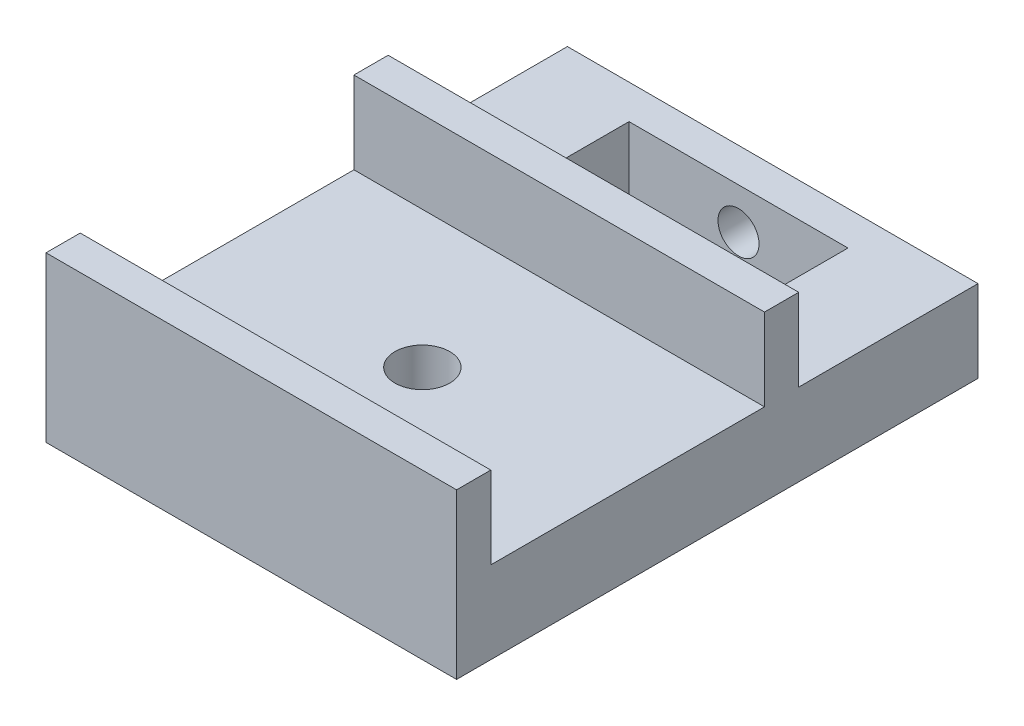
SolidWorks part; units mm, degrees
ref_plane "Front" through (0, 0, 0) normal (0, 0, 1) x (1, 0, 0)
ref_plane "Top" through (0, 0, 0) normal (0, 1, 0) x (1, 0, 0)
ref_plane "Right" through (0, 0, 0) normal (1, 0, 0) x (0, 0, -1)
sketch "Sketch1" plane through (0, 0, 0) normal (0, 1, 0) x (1, 0, 0)
  line L0 (0, -20) -> (0, -22.5)
  line L1 (0, 0) -> (-30, 0)
  line L2 (0, 0) -> (0, -20)
  line L3 (0, -20) -> (-30, -20)
  line L4 (-30, 0) -> (-30, -20)
  line L5 (0, -22.5) -> (-30, -22.5)
  line L6 (-30, -22.5) -> (-30, -20)
  line L7 (0, 0) -> (-7, 0)
  line L8 (-30, 0) -> (0, 0)
  line L9 (-30, 0) -> (-30, 2.5)
  line L10 (-30, 2.5) -> (0, 2.5)
  line L11 (0, 0) -> (0, 2.5)
  line L12 (-30, 0) -> (-23, 0)
  line L13 (-30, 2.5) -> (-30, 13.1)
  line L14 (-30, 13.1) -> (0, 13.1)
  line L15 (0, 13.1) -> (0, 2.5)
  line L16 (0, 13.1) -> (0, 15.6)
  line L17 (0, 15.6) -> (-30, 15.6)
  line L18 (-30, 15.6) -> (-30, 13.1)
  line L19 (-7, 0) -> (-7, 15.6)
  line L20 (-23, 0) -> (-23, 15.6)
  dimension "D1" = 20
  dimension "D2" = 2.5
  dimension "D3" = 2.5
  dimension "D4" = 30
  dimension "D5" = 7
  dimension "D6" = 7
  dimension "D7" = 10.6
  dimension "D8" = 2.5
extrude "Boss-Extrude1" add sketch "Sketch1" along normal blind 6 contours L1 L8 L4 L3 L2 | L6 L5 L0 L3 | L20 L1 L19 L10 | L19 L1 L11 L10 | L19 L10 L15 L14 | L19 L14 L16 L17 | L20 L14 L19 L17 | L14 L20 L17 L18 | L10 L20 L14 L13 | L8 L20 L10 L9 region at (-15, 0, 10) region at (-15, 0, 21.25) region at (-3.5, 0, -1.25) region at (-15, 0, -1.25) region at (-3.5, 0, -7.8) region at (-26.5, 0, -1.25) region at (-3.5, 0, -14.35) region at (-26.5, 0, -7.8) region at (-15, 0, -14.35) region at (-26.5, 0, -14.35)
extrude "Boss-Extrude2" add sketch "Sketch1<3>" along normal blind 12 contours L19 L1 L11 L10 | L20 L1 L19 L10 | L6 L5 L0 L3 | L8 L20 L10 L9 region at (-15, 0, 21.25) region at (-3.5, 0, -1.25) region at (-15, 0, -1.25) region at (-26.5, 0, -1.25)
sketch "Sketch1<3>" plane through (0, 0, 0) normal (0, 1, 0) x (1, 0, 0) same geometry as "Sketch1"
sketch "Sketch3" plane through (0, 0, -15.6) normal (0, 0, -1) x (-1, 0, 0)
  line L0 (30, 3) -> (23, 3)
  line L1 (30, 6) -> (30, 0) construction
  line L2 (23, 3) -> (15, 3)
  circle A0 centre (15, 3) radius 1.5
  dimension "D1" = 7
  dimension "D2" = 8
extrude "Cut-Extrude2" cut sketch "Sketch3" against normal blind 15 contours A0
ref_plane "Plane1" through (0, 0, 10) normal (0, 0, -1) x (-1, 0, 0)
sketch "Sketch2" plane through (0, 6, 0) normal (0, 1, 0) x (1, 0, 0)
  line L0 (-30, -10) -> (0, -10)
  line L1 (-30, 0) -> (-30, -20) construction
  line L2 (0, 0) -> (0, -20) construction
  circle A0 centre (-15, -10) radius 2
extrude "Cut-Extrude1" cut sketch "Sketch2" against normal through all contours L0 A0 | L0 A0 region at (-15, 6, 9.1512) region at (-15, 6, 10.8488)
